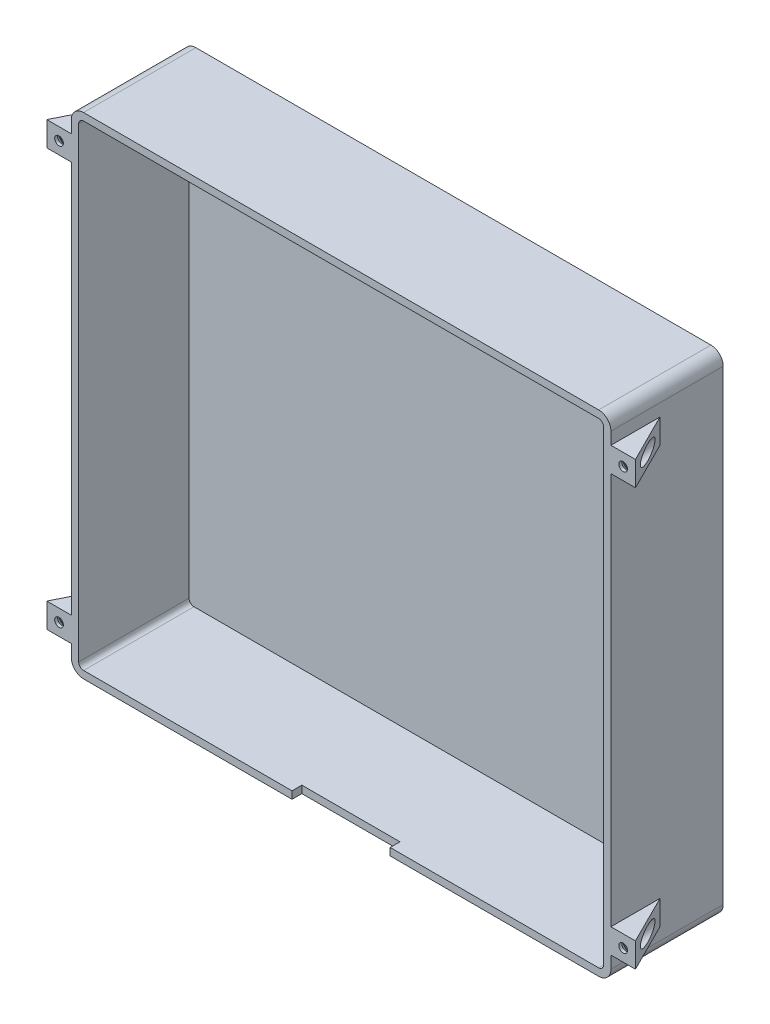
SolidWorks part; units mm, degrees
ref_plane "Front Plane" through (0, 0, 0) normal (0, 0, 1) x (1, 0, 0)
ref_plane "Top Plane" through (0, 0, 0) normal (0, 1, 0) x (1, 0, 0)
ref_plane "Right Plane" through (0, 0, 0) normal (1, 0, 0) x (0, 0, -1)
sketch "Sketch2" plane through (0, 0, 0) normal (0, 0, 1) x (1, 0, 0)
  line L5 (139.7, 127) -> (-139.7, 127)
  line L6 (139.7, 127) -> (139.7, -127)
  line L7 (139.7, -127) -> (-139.7, -127)
  line L8 (-139.7, 127) -> (-139.7, -127)
  line L9 (139.7, 127) -> (-139.7, -127) construction
  line L10 (139.7, -127) -> (-139.7, 127) construction
  point P0 (0, 0)
  dimension "D1" = 254
  dimension "D2" = 279.4
extrude "Boss-Extrude1" add sketch "Sketch2" along normal blind 1
fillet "Fillet2" radius 6.35 4 edges at (139.7, -127, 0.5) (-139.7, -127, 0.5) (-139.7, 127, 0.5) (139.7, 127, 0.5)
sketch "Sketch5" plane through (0, 0, 1) normal (0, 0, 1) x (1, 0, 0)
  line L0 (-133.35, -123.19) -> (133.35, -123.19)
  line L1 (135.89, -120.65) -> (135.89, 120.65)
  line L2 (133.35, 123.19) -> (-133.35, 123.19)
  line L3 (-135.89, 120.65) -> (-135.89, -120.65)
  line L4 (-133.35, -127) -> (133.35, -127)
  line L5 (139.7, -120.65) -> (139.7, 120.65)
  line L6 (133.35, 127) -> (-133.35, 127)
  line L7 (-139.7, 120.65) -> (-139.7, -120.65)
  line L8 (-133.35, -127) -> (133.35, -127)
  line L9 (139.7, -120.65) -> (139.7, 120.65)
  line L10 (133.35, 127) -> (-133.35, 127)
  line L11 (-139.7, 120.65) -> (-139.7, -120.65)
  arc A0 (133.35, -123.19) -> (135.89, -120.65) centre (133.35, -120.65) ccw
  arc A1 (135.89, 120.65) -> (133.35, 123.19) centre (133.35, 120.65) ccw
  arc A2 (-133.35, 123.19) -> (-135.89, 120.65) centre (-133.35, 120.65) ccw
  arc A3 (-135.89, -120.65) -> (-133.35, -123.19) centre (-133.35, -120.65) ccw
  arc A4 (133.35, -127) -> (139.7, -120.65) centre (133.35, -120.65) ccw
  arc A5 (139.7, 120.65) -> (133.35, 127) centre (133.35, 120.65) ccw
  arc A6 (-133.35, 127) -> (-139.7, 120.65) centre (-133.35, 120.65) ccw
  arc A7 (-139.7, -120.65) -> (-133.35, -127) centre (-133.35, -120.65) ccw
  arc A8 (133.35, -127) -> (139.7, -120.65) centre (133.35, -120.65) ccw
  arc A9 (139.7, 120.65) -> (133.35, 127) centre (133.35, 120.65) ccw
  arc A10 (-133.35, 127) -> (-139.7, 120.65) centre (-133.35, 120.65) ccw
  arc A11 (-139.7, -120.65) -> (-133.35, -127) centre (-133.35, -120.65) ccw
  dimension "D1" = 0
  dimension "D2" = 3.81
extrude "Boss-Extrude3" add sketch "Sketch5" along normal blind 57.15
sketch "Sketch7" plane through (0, -123.19, 0) normal (0, 1, 0) x (1, 0, 0)
  line L0 (-133.35, -58.15) -> (133.35, -58.15) construction
  line L1 (25.4, -58.15) -> (-25.4, -58.15)
  line L2 (25.4, -58.15) -> (25.4, -53.07)
  line L3 (25.4, -53.07) -> (-25.4, -53.07)
  line L4 (-25.4, -58.15) -> (-25.4, -53.07)
  point P6 (0, -58.15)
  point P7 (0, 0)
  dimension "D1" = 5.08
  dimension "D2" = 50.8
extrude "Cut-Extrude1" cut sketch "Sketch7" against normal blind 57.15
ref_plane "Plane1" through (0, 101.6, 0) normal (0, 1, 0) x (1, 0, 0)
sketch "Sketch8" plane through (0, 101.6, 0) normal (0, 1, 0) x (1, 0, 0)
  line L0 (-139.7, 0) -> (-152.4, 0)
  line L1 (-152.4, 0) -> (-139.7, -25.4)
  line L2 (-139.7, -58.15) -> (-139.7, 0) construction
  line L3 (-139.7, -25.4) -> (-139.7, 0)
  line L4 (139.7, 0) -> (139.7, -25.4) construction
  line L5 (139.7, 0) -> (139.7, -58.15) construction
  line L6 (139.7, -25.4) -> (152.4, 0) construction
  line L7 (152.4, 0) -> (139.7, 0) construction
  dimension "D1" = 12.7
  dimension "D2" = 25.4
extrude "Boss-Extrude4" add sketch "Sketch8" along normal blind 12.7
ref_plane "Plane2" through (0, 0, 3.81) normal (0, 0, -1) x (-1, 0, 0)
sketch "Sketch9" plane through (0, 0, 3.81) normal (0, 0, -1) x (-1, 0, 0)
  line L0 (152.4, 114.3) -> (152.4, 101.6) construction
  line L1 (152.4, 114.3) -> (152.4, 101.6)
  line L2 (152.4, 107.95) -> (146.05, 107.95)
  circle A0 centre (146.05, 107.95) radius 3.81
  point P5 (145.7892, 107.95)
  dimension "D1" = 7.62
  dimension "D2" = 6.35
extrude "Cut-Extrude2" cut sketch "Sketch9" against normal blind 35.306 contours A0
hole_wizard "CSK for #8 Flat Head Machine Screw1" positions "Sketch12" profile "Sketch13" countersink size "#8" standard "ANSI Inch" end condition through all
sketch "Sketch12" plane through (0, 0, 3.81) normal (0, 0, 1) x (1, 0, 0)
  point P0 (-146.05, 107.95)
sketch "Sketch13" plane through (-146.05, 107.95, 3.81) normal (1, 0, 0) x (0, -1, 0)
  line L0 (0, 0) -> (0, 3.81)
  line L1 (0, 3.81) -> (2.2479, 3.81)
  line L2 (2.2479, 3.81) -> (2.2479, 2.2645)
  line L3 (2.2479, 2.2645) -> (4.2164, 0)
  line L5 (4.2164, 0) -> (0, 0)
  line L6 (-2.2479, 2.2645) -> (-4.2164, 0) construction
  line L11 (0, -6.35) -> (0, 107.95) construction
  dimension "Thru Hole Dia." = 4.4958
  dimension "Thru Hole Depth" = 3.81
  dimension "Near C'Sink Dia." = 8.4328
  dimension "Near C'Sink Angle" = 82
sketch "Sketch14" plane through (0, 0, 3.81) normal (0, 0, -1) x (-1, 0, 0)
  line L1 (159.8523, 111.76) -> (146.05, 111.76)
  line L2 (159.8523, 111.76) -> (159.8523, 104.14)
  line L3 (159.8523, 104.14) -> (146.05, 104.14)
  line L4 (146.05, 111.76) -> (146.05, 104.14)
  circle A0 centre (146.05, 107.95) radius 2.2479 construction
  circle A1 centre (146.05, 107.95) radius 2.2479 construction
  circle A2 centre (146.05, 107.95) radius 3.81 construction
  point P7 (0, 0)
ref_plane "Plane3" through (0, 0, 0) normal (0, 1, 0) x (1, 0, 0)
mirror "Mirror2" about plane through (0, 0, 0) normal (0, 1, 0) of "Cut-Extrude2", "CSK for #8 Flat Head Machine Screw1", "Boss-Extrude4"
ref_plane "Plane4" through (0, 0, 0) normal (-1, 0, 0) x (0, 0, 1)
mirror "Mirror3" about plane through (0, 0, 0) normal (-1, 0, 0) of "Mirror2", "CSK for #8 Flat Head Machine Screw1", "Cut-Extrude2", "Boss-Extrude4"
ref_plane "Plane5" through (0, 0, 29.075) normal (0, 0, -1) x (-1, 0, 0)
mirror "Mirror4" about plane through (0, 0, 29.075) normal (0, 0, -1) of "Mirror3", "Mirror2", "CSK for #8 Flat Head Machine Screw1", "Cut-Extrude2", "Boss-Extrude4"
sketch "Sketch15" plane through (0, 0, 0) normal (0, 0, -1) x (-1, 0, 0)
  line L1 (-152.4, 114.3) -> (-139.7, 114.3)
  line L2 (-152.4, 114.3) -> (-152.4, -114.3)
  line L3 (-152.4, -114.3) -> (-139.7, -114.3)
  line L4 (-139.7, 114.3) -> (-139.7, -114.3)
  line L5 (152.4, -114.3) -> (139.7, -114.3)
  line L6 (152.4, -114.3) -> (152.4, 114.3)
  line L7 (152.4, 114.3) -> (139.7, 114.3)
  line L8 (139.7, -114.3) -> (139.7, 114.3)
extrude "Cut-Extrude4" cut sketch "Sketch15" against normal blind 30.226
sketch "Sketch17" [suppressed] plane through (0, 127, 0) normal (0, 1, 0) x (1, 0, 0)
  line L4 (98.4433, -33.0881) -> (98.4433, -48.0233)
  line L5 (98.4433, -48.0233) -> (119.2713, -48.0233)
  line L6 (119.2713, -48.0233) -> (119.2713, -33.0881)
  line L7 (119.2713, -33.0881) -> (98.4433, -33.0881)
  line L8 (98.4433, -33.0881) -> (98.4433, -48.0233)
  line L9 (98.4433, -48.0233) -> (119.2713, -48.0233)
  line L10 (119.2713, -48.0233) -> (119.2713, -33.0881)
  line L11 (119.2713, -33.0881) -> (98.4433, -33.0881)
  circle A0 centre (-108.6948, -25.9909) radius 1.632 construction
  circle A1 centre (-25.8908, -25.9909) radius 1.632 construction
  circle A2 centre (98.0996, -15.605) radius 6.9215 construction
  circle A3 centre (-108.6948, -25.9909) radius 1.632
  circle A4 centre (-25.8908, -25.9909) radius 1.632
  circle A5 centre (98.0996, -15.605) radius 6.9215
  point P13 (0, 0)
  point P14 (0, 0)
  dimension "D1" = 0
sketch "Sketch18" [suppressed] plane through (0, 123.19, 0) normal (0, -1, 0) x (1, 0, 0)
  line L0 (133.35, 1) -> (-133.35, 1) construction
  line L1 (-16.3658, 1) -> (-35.4158, 1)
  line L2 (-118.2198, 1) -> (-118.2198, 25.9909)
  line L3 (-99.1698, 25.9909) -> (-99.1698, 1)
  line L4 (-99.1698, 1) -> (-118.2198, 1)
  line L5 (-35.4158, 1) -> (-35.4158, 25.9909)
  line L6 (-16.3658, 25.9909) -> (-16.3658, 1)
  line L7 (-16.3658, 1) -> (-35.4158, 1)
  line L8 (-99.1698, 1) -> (-118.2198, 1)
  arc A2 (-118.2198, 25.9909) -> (-99.1698, 25.9909) centre (-108.6948, 25.9909) cw
  arc A3 (-35.4158, 25.9909) -> (-16.3658, 25.9909) centre (-25.8908, 25.9909) cw
  point P13 (0, 0)
  point P15 (0, 0)
  line M2 (-133.35, 1) -> (133.35, 1)
  dimension "D1" = 9.525
extrude "Boss-Extrude5" [suppressed] add sketch "Sketch18" along normal blind 12.7 contours A2 L2 L3 M2 | A3 L5 L6 M2
sketch "Sketch19" [suppressed] plane through (0, 127, 0) normal (0, 1, 0) x (1, 0, 0)
  circle A0 centre (-108.6948, -25.9909) radius 1.27
  circle A1 centre (-25.8908, -25.9909) radius 1.27
  dimension "D1" = 2.54
extrude "Cut-Extrude5" [suppressed] cut sketch "Sketch19" against normal up to next
